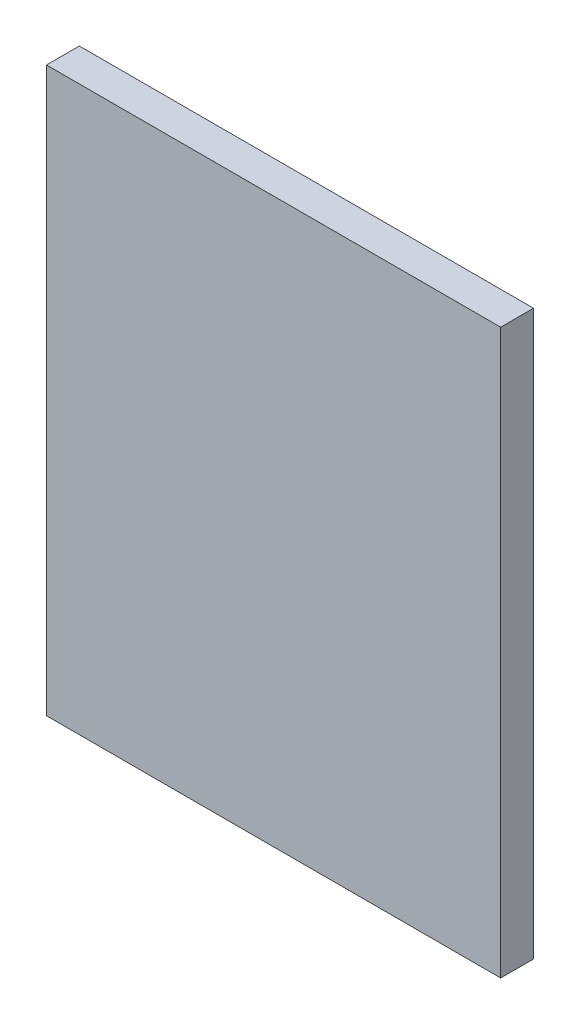
SolidWorks part; units mm, degrees
material "Pine"
ref_plane "Front Plane" through (0, 0, 0) normal (0, 0, 1) x (1, 0, 0)
ref_plane "Top Plane" through (0, 0, 0) normal (0, 1, 0) x (1, 0, 0)
ref_plane "Right Plane" through (0, 0, 0) normal (1, 0, 0) x (0, 0, -1)
sketch "Sketch3" plane through (0, 0, 0) normal (0, 0, 1) x (1, 0, 0)
  line L4 (417, 206) -> (583, 206)
  line L5 (417, 206) -> (417, 0)
  line L6 (417, 0) -> (583, 0)
  line L7 (583, 206) -> (583, 0)
  line L8 (417, 206) -> (583, 0) construction
  line L9 (417, 0) -> (583, 206) construction
  point P6 (500, 103)
  dimension "D1" = 166
  dimension "D2" = 206
extrude "Boss-Extrude2" add sketch "Sketch3" along normal blind 12 separate body
equation "\"LENGTH\" = 1000mm"
equation "\"PLY\"= 12mm"
equation "\"CENTER_BRACE_LENGTH\" = 393mm"
equation "\"PANEL_WIDTH\"= \"LENGTH\" - \"CENTER_BRACE_LENGTH\" * 2 - \"PLY\" * 4"
equation "\"D1@Boss-Extrude2\"=\"PLY\""
equation "\"D1@Sketch3\"=\"PANEL_WIDTH\""
equation "\"PANEL_SMALL_HEIGHT\" = 70mm"
equation "\"D2@Sketch3\"=\"WIDTH\" - \"PLY\" * 2 - \"PANEL_SMALL_HEIGHT\""
equation "\"WIDTH\" = 300mm"
